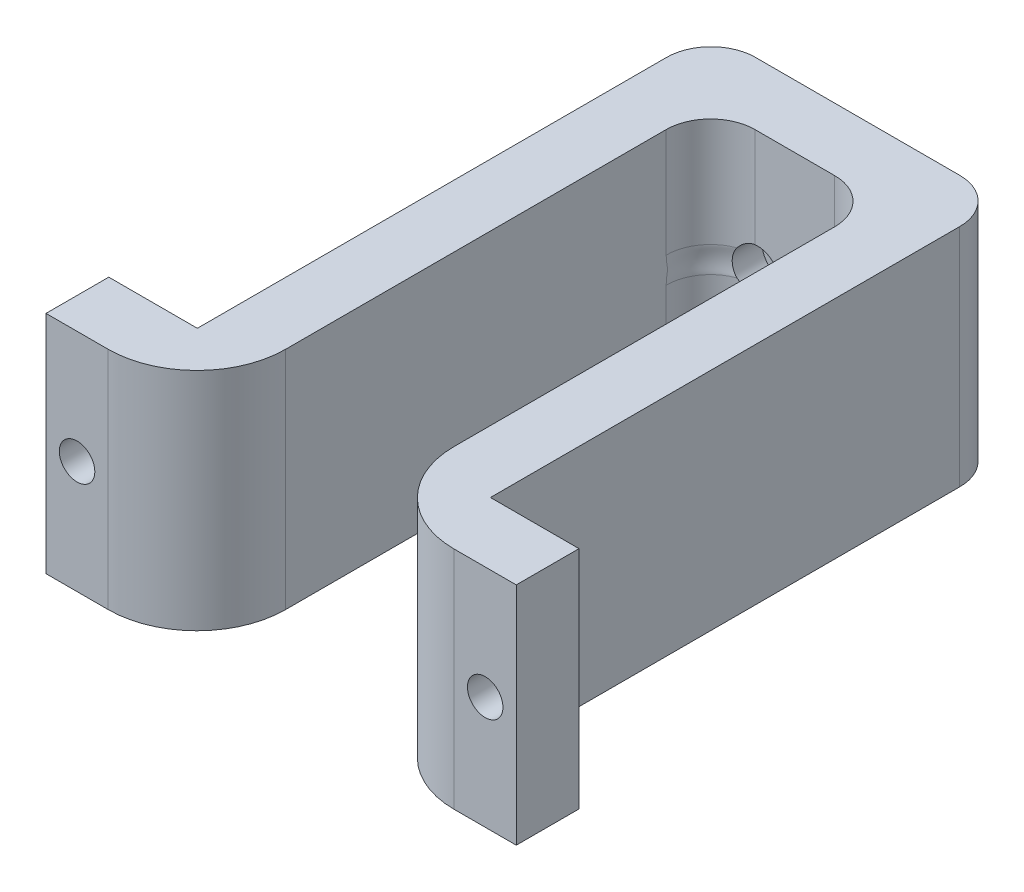
SolidWorks part; units mm, degrees
ref_plane "Front Plane" through (0, 0, 0) normal (0, 0, 1) x (1, 0, 0)
ref_plane "Top Plane" through (0, 0, 0) normal (0, 1, 0) x (1, 0, 0)
ref_plane "Right Plane" through (0, 0, 0) normal (1, 0, 0) x (0, 0, -1)
sketch "Sketch1" plane through (0, 0, 0) normal (0, 1, 0) x (1, 0, 0)
  line L0 (-13, 0) -> (13, 0)
  line L2 (-9.49, -25.4) -> (-16.51, -25.4)
  line L3 (-9.49, -25.4) -> (-9.49, 25.4)
  line L4 (-9.49, 25.4) -> (-16.51, 25.4)
  line L5 (-16.51, -25.4) -> (-16.51, 25.4)
  line L6 (-9.49, -25.4) -> (-16.51, 25.4) construction
  line L7 (-9.49, 25.4) -> (-16.51, -25.4) construction
  line L8 (9.49, -25.4) -> (16.51, -25.4)
  line L9 (9.49, -25.4) -> (9.49, 25.4)
  line L10 (9.49, 25.4) -> (16.51, 25.4)
  line L11 (16.51, -25.4) -> (16.51, 25.4)
  line L12 (9.49, -25.4) -> (16.51, 25.4) construction
  line L13 (9.49, 25.4) -> (16.51, -25.4) construction
  line L14 (-16.51, 25.4) -> (16.51, 25.4)
  line L15 (-16.51, 25.4) -> (-16.51, 32.4712)
  line L16 (-16.51, 32.4712) -> (16.51, 32.4712)
  line L17 (16.51, 25.4) -> (16.51, 32.4712)
  line L18 (-9.49, -25.4) -> (-26.49, -25.4)
  line L19 (-9.49, -25.4) -> (-9.49, -32.4712)
  line L20 (-9.49, -32.4712) -> (-26.49, -32.4712)
  line L21 (-26.49, -25.4) -> (-26.49, -32.4712)
  line L22 (9.49, -25.4) -> (26.49, -25.4)
  line L23 (9.49, -25.4) -> (9.49, -32.4712)
  line L24 (9.49, -32.4712) -> (26.49, -32.4712)
  line L25 (26.49, -25.4) -> (26.49, -32.4712)
  point P4 (0, 0)
  dimension "D1" = 50.8
  dimension "D2" = 7.0712
  dimension "D3" = 17
  dimension "D4" = 33.02
  dimension "D5" = 7.02
extrude "Boss-Extrude1" add sketch "Sketch1" along normal blind 25.4 contours L5 L2 L3 L4 | L10 L17 L16 L15 L4 L14 | L8 L11 L10 L9 | L19 L18 L21 L20 | L23 L22 L25 L24 region at (-10.0028, 0, 12.7) region at (10.0028, 0, -12.7) region at (0, 0, -28.9356)
fillet "Fillet1" radius 10 2 edges at (9.49, 12.7, 32.4712) (-9.49, 12.7, 32.4712)
fillet "Fillet2" radius 5 2 edges at (16.51, 12.7, -32.4712) (-16.51, 12.7, -32.4712)
sketch "Sketch3" plane through (0, 0, 32.4712) normal (0, 0, 1) x (1, 0, 0)
  line L3 (0, -35.7184) -> (0, 35.7184) construction
  circle A0 centre (-22.99, 12.7) radius 2
  circle A1 centre (22.99, 12.7) radius 2
  point P7 (-22.99, 12.7)
extrude "Cut-Extrude1" cut sketch "Sketch3" against normal through all
sketch "Sketch4" plane through (0, 0, -32.4712) normal (0, 0, -1) x (-1, 0, 0)
  line L3 (0, 25.4) -> (0, 0) construction
  line L4 (11.51, 25.4) -> (-11.51, 25.4) construction
  circle A0 centre (-4.1881, 11.684) radius 1.5
  circle A1 centre (4.1881, 11.684) radius 1.5
extrude "Cut-Extrude2" cut sketch "Sketch4" against normal through all
fillet "Fillet3" radius 5 2 edges at (-9.49, 12.7, -25.4) (9.49, 12.7, -25.4)
sketch "Sketch7" plane through (0, 0, -25.4) normal (0, 0, 1) x (1, 0, 0)
  circle A0 centre (-4.1881, 11.684) radius 2.5
  circle A1 centre (4.1881, 11.684) radius 2.5
  dimension "D1" = 5
extrude "Cut-Extrude3" cut sketch "Sketch7" against normal mid plane 6
